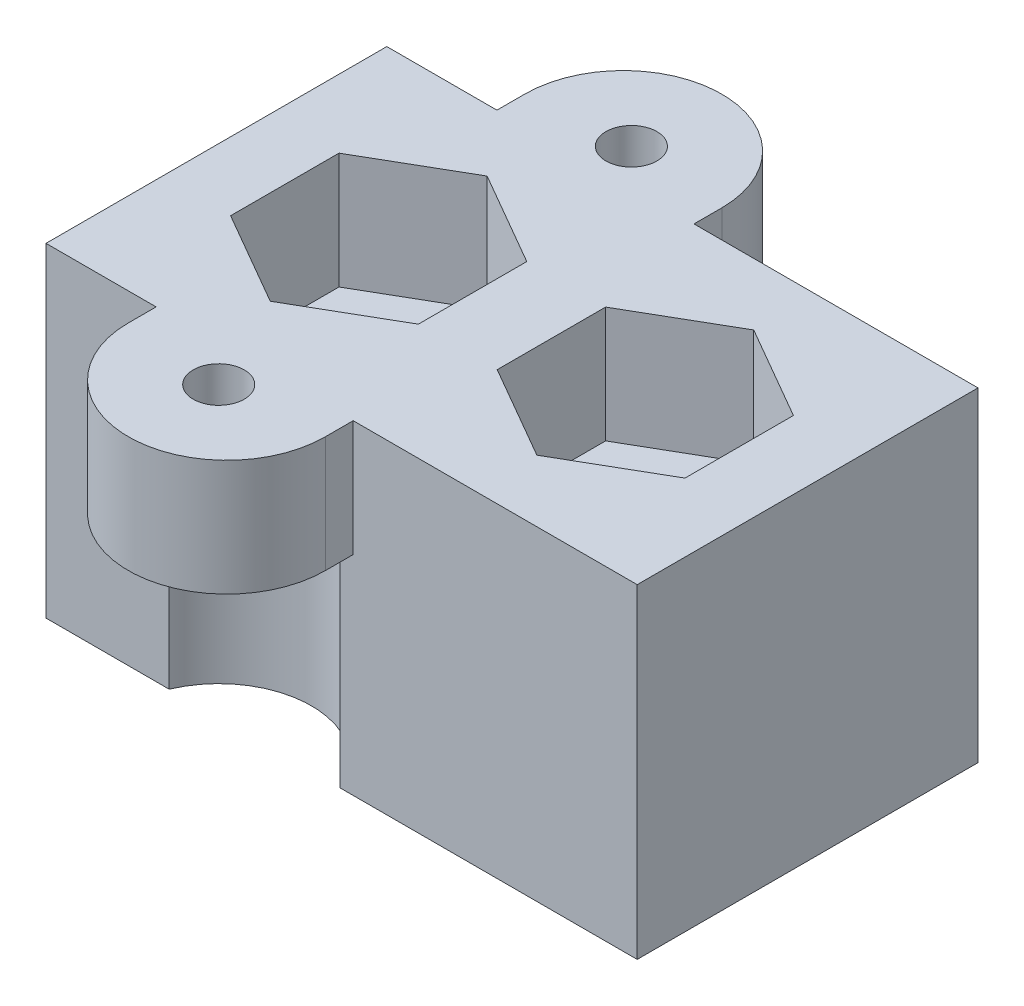
SolidWorks part; units mm, degrees
ref_plane "前视基准面" through (0, 0, 0) normal (0, 0, 1) x (1, 0, 0)
ref_plane "上视基准面" through (0, 0, 0) normal (0, 1, 0) x (1, 0, 0)
ref_plane "右视基准面" through (0, 0, 0) normal (1, 0, 0) x (0, 0, -1)
sketch "草图1" plane through (0, 0, 0) normal (0, 1, 0) x (1, 0, 0)
  line L0 (4.0406, 7.35) -> (4.0406, -7.35) construction
  line L7 (4.0406, -7.35) -> (29.5406, -7.35)
  line L8 (4.0406, -7.35) -> (4.0406, 7.35)
  line L11 (4.0406, 7.35) -> (29.5406, 7.35)
  line L12 (29.5406, -7.35) -> (29.5406, 7.35)
  line L13 (29.5406, -1.4) -> (29.5406, 1.4) construction
  line L14 (17.2906, 7.35) -> (8.7906, 7.35) construction
  line L15 (17.2906, -7.35) -> (8.7906, -7.35) construction
extrude "主体" add sketch "草图1" along normal blind 14
sketch "草图4" plane through (0, 14, 0) normal (0, -1, 0) x (1, 0, 0)
  line L0 (8.7906, -7.35) -> (8.7906, -8.55) construction
  line L1 (8.7906, -7.35) -> (17.2906, -7.35)
  line L2 (8.7906, -7.35) -> (8.7906, -12.8)
  line L3 (8.7906, -12.8) -> (17.2906, -12.8)
  line L4 (17.2906, -7.35) -> (17.2906, -12.8)
  line L6 (11.149, -12.8) -> (22.4321, -12.8) construction
  point P6 (0, 0)
  point P7 (0, 0)
  point P9 (0, 0)
extrude "凸台-拉伸2" add sketch "草图4" along normal blind 5
fillet "圆角1" 2 edges at (8.7906, 11.5, -12.8) (17.2906, 11.5, -12.8) type full round first side face at (8.7906, 11.5, -10.075) second side face at (17.2906, 11.5, -10.075) middle face at (13.0406, 11.5, -12.8)
hole_wizard "M2 间隙孔1" positions "草图5" profile "草图6" hole size "M2" standard "ISO" end condition up to next
sketch "草图5" plane through (0, 9, 0) normal (0, -1, 0) x (-1, 0, 0)
  point P0 (-13.0406, 8.9)
  point P3 (0, 0)
sketch "草图6" plane through (13.0406, 9, -8.9) normal (1, 0, 0) x (0, 0, -1)
  line L0 (0, 0) -> (0, 5)
  line L1 (0, 5) -> (1.1, 5)
  line L2 (1.1, 5) -> (1.1, 0)
  line L5 (1.1, 0) -> (0, 0)
  line L11 (0, -6.35) -> (0, 107.95) construction
  dimension "通孔孔直径" = 2.2
  dimension "通孔孔深度" = 5
sketch "草图7" plane through (0, 0, 0) normal (0, -1, 0) x (1, 0, 0)
  circle A0 centre (13.0406, -8.9) radius 4
  point P2 (0, 0)
extrude "切除-拉伸3" cut sketch "草图7" against normal up to surface (9 mm away) up to face at (13.0406, 9, -10)
mirror "镜向1" about plane through (0, 0, 0) normal (0, 0, 1) of "切除-拉伸3", "M2 间隙孔1", "圆角1", "凸台-拉伸2"
hole_wizard "M5 间隙孔1" positions "草图8" profile "草图9" hole size "M5" standard "ISO" end condition up to next
sketch "草图8" plane through (0, 0, 0) normal (0, -1, 0) x (-1, 0, 0)
  line L0 (-7.7, 0) -> (7.7, 0) construction
  line L1 (-29.5406, -7.35) -> (-29.5406, 7.35) construction
  line L2 (-4.0406, 7.35) -> (-4.0406, -7.35) construction
  point P0 (-22.5406, 0)
  point P2 (-11.0406, 0)
  point P5 (0, 0)
  point P8 (0, 0)
  dimension "D1" = 7
  dimension "D2" = 7
  dimension "D3" = 11.5
sketch "草图9" plane through (22.5406, 0, 0) normal (1, 0, 0) x (0, 0, -1)
  line L0 (0, 0) -> (0, 14)
  line L1 (0, 14) -> (2.65, 14)
  line L2 (2.65, 14) -> (2.65, 0)
  line L5 (2.65, 0) -> (0, 0)
  line L11 (0, -6.35) -> (0, 107.95) construction
  dimension "通孔孔直径" = 5.3
  dimension "通孔孔深度" = 14
sketch "草图10" plane through (0, 14, 0) normal (0, 1, 0) x (1, 0, 0)
  line L1 (11.0406, 4.6765) -> (6.9906, 2.3383)
  line L2 (6.9906, 2.3383) -> (6.9906, -2.3383)
  line L3 (6.9906, -2.3383) -> (11.0406, -4.6765)
  line L4 (11.0406, -4.6765) -> (15.0906, -2.3383)
  line L5 (15.0906, -2.3383) -> (15.0906, 2.3383)
  line L6 (15.0906, 2.3383) -> (11.0406, 4.6765)
  line L7 (22.5406, 4.6765) -> (18.4906, 2.3383)
  line L8 (18.4906, 2.3383) -> (18.4906, -2.3383)
  line L9 (18.4906, -2.3383) -> (22.5406, -4.6765)
  line L10 (22.5406, -4.6765) -> (26.5906, -2.3383)
  line L11 (26.5906, -2.3383) -> (26.5906, 2.3383)
  line L12 (26.5906, 2.3383) -> (22.5406, 4.6765)
  circle A0 centre (11.0406, 0) radius 4.05 construction
  circle A1 centre (22.5406, 0) radius 4.05 construction
  point P9 (0, 0)
  point P17 (0, 0)
extrude "切除-拉伸4" cut sketch "草图10" against normal blind 5
